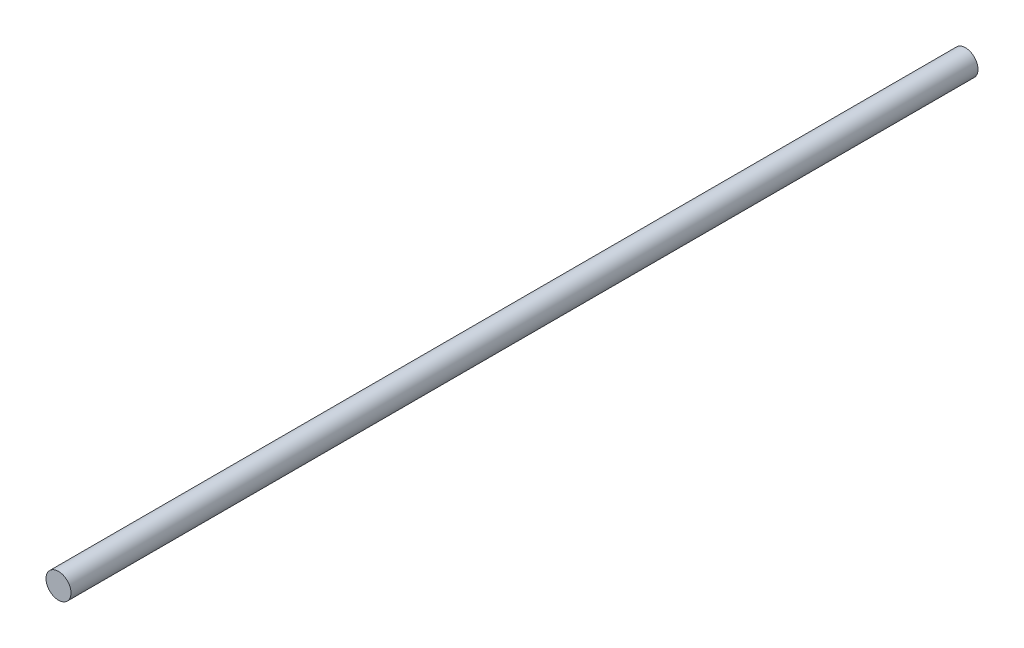
SolidWorks part; units mm, degrees
ref_plane "Front Plane" through (0, 0, 0) normal (0, 0, 1) x (1, 0, 0)
ref_plane "Top Plane" through (0, 0, 0) normal (0, 1, 0) x (1, 0, 0)
ref_plane "Right Plane" through (0, 0, 0) normal (1, 0, 0) x (0, 0, -1)
sketch "Sketch1" plane through (0, 0, 0) normal (0, 0, 1) x (1, 0, 0)
  circle A0 centre (0, 0) radius 4
  dimension "D1" = 8
extrude "Boss-Extrude1" add sketch "Sketch1" against normal blind 290
ref_plane "Plane2" through (0, 0, 1) normal (0, 0, 1) x (1, 0, 0)
sketch "Sketch2" plane through (0, 0, 1) normal (0, 0, 1) x (1, 0, 0)
  circle A1 centre (0, 0) radius 4.05
  dimension "D1" = 8.1
curve "Helix/Spiral1" pitch 8 height 290 turns 36.25
sketch "Sketch3" plane through (0, 0, 1) normal (0, 0, 1) x (1, 0, 0)
  circle A0 centre (0, 0) radius 4
  circle A1 centre (0, 0) radius 4
  circle A2 centre (0, 0) radius 4
  dimension "D1" = 0
sketch "Sketch4" plane through (0, 0, 1) normal (0, 0, 1) x (1, 0, 0)
  circle A0 centre (0, 0) radius 4 construction
  circle A1 centre (0, 0) radius 4
curve "Helix/Spiral2" pitch 8 height 290 turns 36.25
sketch "Sketch5" plane through (0, 0, 1) normal (0, 0, 1) x (1, 0, 0)
  circle A0 centre (0, 0) radius 4 construction
  circle A1 centre (0, 0) radius 4
curve "Helix/Spiral3" pitch 8 height 290 turns 36.25
sketch "Sketch6" plane through (0, 0, 1) normal (0, 0, 1) x (1, 0, 0)
  circle A0 centre (0, 0) radius 4 construction
  circle A1 centre (0, 0) radius 4
curve "Helix/Spiral4" pitch 8 height 290 turns 36.25
sketch "Sketch10" plane through (0, 0, 0) normal (0, 1, 0) x (1, 0, 0)
  line L0 (4.05, -1.67) -> (4.05, -0.33)
  line L1 (2.9, -1.3619) -> (2.9, -0.6519)
  line L2 (2.9, -1.3619) -> (4.05, -1.67)
  line L7 (2.9, -0.6519) -> (4.05, -0.33)
  point P4 (4.05, -1)
  dimension "D6" = 0.71
  dimension "D9" = 1.34
  dimension "D10" = 75
  dimension "D11" = 1.15
sweep "Cut-Sweep3" [suppressed] cut profiles "Sketch10" path "Helix/Spiral1"
sketch "Sketch11" plane through (0, 0, 0) normal (1, 0, 0) x (0, 0, -1)
  line L0 (2.33, -4) -> (3.67, -4)
  line L5 (-1, 4) -> (2.9931, -2.85) construction
  line L6 (2.33, -4) -> (2.6381, -2.85)
  line L7 (3.67, -4) -> (3.3481, -2.85)
  line L8 (2.6381, -2.85) -> (3.3481, -2.85)
  dimension "D1" = 1.34
sweep "Cut-Sweep4" [suppressed] cut profiles "Sketch11" path "Helix/Spiral2"
sketch "Sketch12" plane through (0, 0, 1) normal (0, 0, 1) x (1, 0, 0)
  line L0 (-4, 0) -> (4, 0) construction
  circle A0 centre (0, 0) radius 4 construction
ref_plane "Plane3" through (0, 0, 0) normal (0, -1, 0) x (-1, 0, 0)
sketch "Sketch13" plane through (0, 0, 0) normal (0, -1, 0) x (-1, 0, 0)
  line L0 (4, -0.33) -> (4, -1.67)
  line L1 (2.85, -0.6419) -> (2.85, -1.3619)
  line L2 (2.85, -1.3619) -> (4, -1.67)
  line L3 (4, -0.33) -> (2.85, -0.6419)
  point P2 (4, -1)
  dimension "D1" = 1.34
  dimension "D2" = 0.72
  dimension "D3" = 1.15
  dimension "D4" = 75
sweep "Cut-Sweep5" [suppressed] cut profiles "Sketch13" path "Helix/Spiral3"
sketch "Sketch14" plane through (0, 0, 0) normal (1, 0, 0) x (0, 0, -1)
  line L0 (-1.67, -4) -> (-0.33, -4)
  line L1 (-1.3619, -2.85) -> (-0.6519, -2.85)
  line L2 (-0.6519, -2.85) -> (-0.33, -4)
  line L3 (-1.67, -4) -> (-1.3619, -2.85)
  point P4 (-1, -4)
  dimension "D1" = 1.34
  dimension "D2" = 0.71
  dimension "D3" = 1.15
  dimension "D4" = 75
sweep "Cut-Sweep6" [suppressed] cut profiles "Sketch14" path "Helix/Spiral4"
equation "\"D3@Helix/Spiral1\" = \"D1@Boss-Extrude1\""
equation "\"D3@Helix/Spiral2\"= \"D1@Boss-Extrude1\""
equation "\"D3@Helix/Spiral3\" = \"D1@Boss-Extrude1\""
equation "\"D3@Helix/Spiral4\"= \"D1@Boss-Extrude1\""
